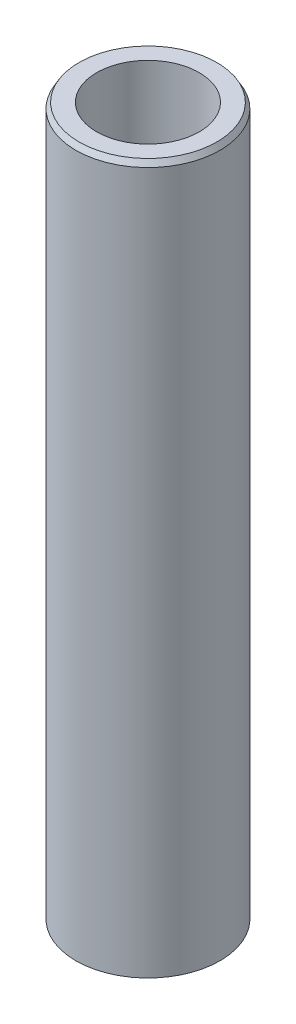
SolidWorks part; units mm, degrees
ref_plane "Front Plane" through (0, 0, 0) normal (0, 0, 1) x (1, 0, 0)
ref_plane "Top Plane" through (0, 0, 0) normal (0, 1, 0) x (1, 0, 0)
ref_plane "Right Plane" through (0, 0, 0) normal (1, 0, 0) x (0, 0, -1)
sketch "Sketch1" plane through (0, 0, 0) normal (0, 1, 0) x (1, 0, 0)
  circle A0 centre (0, 0) radius 32.5
  dimension "SHAFT_OD" = 65
extrude "Boss-Extrude1" add sketch "Sketch1" along normal blind 320.2874
sketch "Sketch2" plane through (0, 0, 0) normal (0, 1, 0) x (1, 0, 0)
  circle A0 centre (0, 0) radius 23.1286
  dimension "BORE_D" = 46.2572
extrude "Cut-Extrude1" cut sketch "Sketch2" along normal through all
chamfer "Chamfer1" distance 2.5234 angle 30 2 edges at (0, 320.2874, 32.5) (0, 0, 32.5) first distance on face at (0, 320.2874, 32.5) first distance on face at (0, 0, 23.1286)
